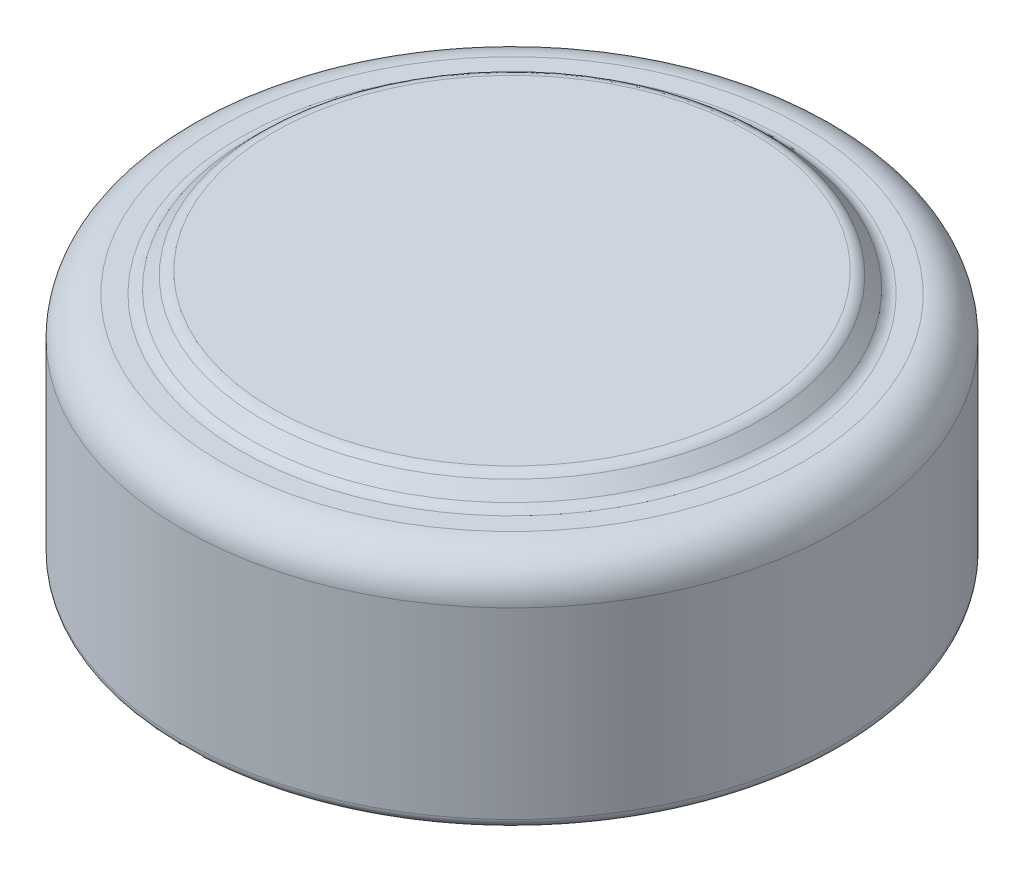
SolidWorks part; units mm, degrees
ref_plane "Front Plane" through (0, 0, 0) normal (0, 0, 1) x (1, 0, 0)
ref_plane "Top Plane" through (0, 0, 0) normal (0, 1, 0) x (1, 0, 0)
ref_plane "Right Plane" through (0, 0, 0) normal (1, 0, 0) x (0, 0, -1)
sketch "Sketch1" plane through (0, 0, 0) normal (0, 0, 1) x (1, 0, 0)
  line L0 (0, 0) -> (-3.3, 0)
  line L1 (-3.4, 0.1) -> (-3.4, 1.99)
  line L2 (-2.4679, 2.6) -> (0, 2.6)
  line L3 (0, 2.6) -> (0, 0)
  line L4 (-2.6961, 2.4339) -> (-2.5739, 2.5561)
  line L7 (-2.8021, 2.39) -> (-3, 2.39)
  arc A0 (-3.4, 1.99) -> (-3, 2.39) centre (-3, 1.99) cw
  arc A1 (-2.4679, 2.6) -> (-2.5739, 2.5561) centre (-2.4679, 2.45) ccw
  arc A2 (-2.8021, 2.39) -> (-2.6961, 2.4339) centre (-2.8021, 2.54) ccw
  arc A3 (-3.3, 0) -> (-3.4, 0.1) centre (-3.3, 0.1) cw
  point P9 (-3.4, 2.39)
  point P13 (-2.74, 2.39)
  point P17 (-3.4, 0)
  point P18 (-2.74, 2.39)
  point P20 (-2.74, 2.39)
  dimension "D6" = 0.4
  dimension "D7" = 0.15
  dimension "D8" = 0.1
  dimension "D1" = 3.4
  dimension "D2" = 2.6
  dimension "D3" = 2.74
  dimension "D4" = 2.39
  dimension "D5" = 45
revolve "Revolve1" add sketch "Sketch1" angle 360 about L3
sketch "Sketch2" plane through (0, 0, 0) normal (0, -1, 0) x (1, 0, 0)
  line L0 (0.25, 0.25) -> (1.5, 0.25)
  line L1 (-0.25, 1.5) -> (0.25, 1.5)
  line L2 (-0.25, 1.5) -> (-0.25, 0.25)
  line L3 (-0.25, -1.5) -> (0.25, -1.5)
  line L4 (0.25, 1.5) -> (0.25, 0.25)
  line L5 (-1.5, 0.25) -> (-0.25, 0.25)
  line L6 (-1.5, 0.25) -> (-1.5, -0.25)
  line L7 (-1.5, -0.25) -> (-0.25, -0.25)
  line L8 (1.5, 0.25) -> (1.5, -0.25)
  line L9 (0.25, -0.25) -> (1.5, -0.25)
  line L10 (0.25, -0.25) -> (0.25, -1.5)
  line L11 (-0.25, -0.25) -> (-0.25, -1.5)
  circle A0 centre (0, 0) radius 2 construction
  text T0 "                SR66" font "Century Gothic" height 1
  dimension "D1" = 4
  dimension "D2" = 0.25
  dimension "D3" = 0.5
  dimension "D4" = 0.25
  dimension "D5" = 0.5
  dimension "D6" = 3
  dimension "D7" = 3
  dimension "D8" = 1.5
  dimension "D9" = 1.5
wrap "Wrap1" sketch "Sketch2" wrap type scribe source sketch "Sketch2" face at (-3.3, 0, 0)
